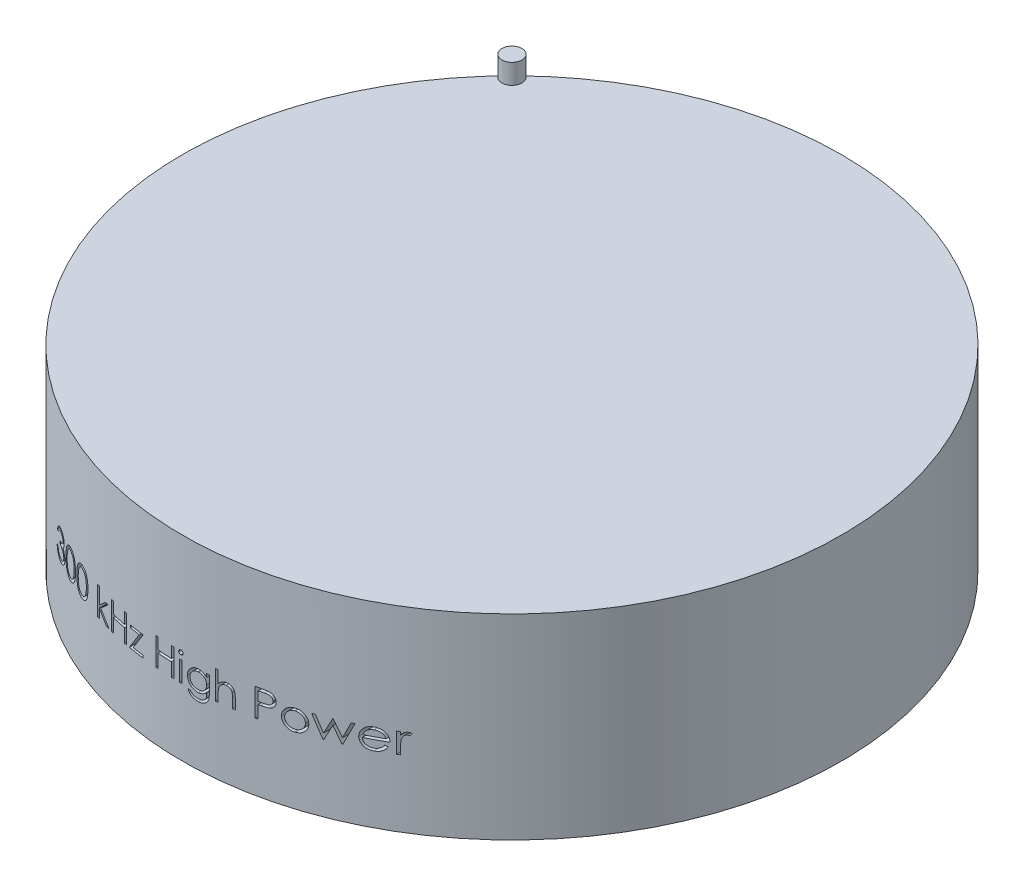
SolidWorks part; units mm, degrees
ref_plane "Front Plane" through (0, 0, 0) normal (0, 0, 1) x (1, 0, 0)
ref_plane "Top Plane" through (0, 0, 0) normal (0, 1, 0) x (1, 0, 0)
ref_plane "Right Plane" through (0, 0, 0) normal (1, 0, 0) x (0, 0, -1)
sketch "Sketch1" plane through (0, 0, 0) normal (0, 0, 1) x (1, 0, 0)
  line L0 (0, 0) -> (0, 29.7209) construction
  line L2 (0, 0) -> (41.9, 0)
  line L3 (0, 0) -> (0, 24.892)
  line L4 (0, 24.892) -> (41.9, 24.892)
  line L5 (41.9, 0) -> (41.9, 24.892)
  dimension "D1" = 83.8
  dimension "D2" = 24.892
revolve "Revolve1" add sketch "Sketch1" angle 360 about L0
sketch "Sketch2" plane through (0, 0, 0) normal (1, 0, 0) x (0, 0, -1)
  line L0 (0, 0) -> (0, 89.4138) construction
  line L2 (0, 56.896) -> (-1.27, 56.896)
  line L3 (0, 56.896) -> (0, 54.356)
  line L4 (0, 54.356) -> (-1.27, 54.356)
  line L5 (-1.27, 56.896) -> (-1.27, 54.356)
  line L6 (41.9, 24.892) -> (-41.9, 24.892) construction
  point P7 (0, 55.626)
  dimension "D1" = 1.27
  dimension "D2" = 2.54
  dimension "D3" = 30.734
revolve "Revolve2" add sketch "Sketch2" angle 360 about L0
sketch "Sketch3" plane through (0, 0, 0) normal (0, 0, 1) x (1, 0, 0)
  line L0 (-41.9, 8.5239) -> (41.9, 8.5239) construction
  line L1 (-41.9, 24.892) -> (-41.9, 0) construction
  line L2 (41.9, 0) -> (41.9, 24.892) construction
  text T0 "300 kHz High Power"
extrude "Cut-Extrude1" cut sketch "Sketch3" against normal blind 12.7 from offset 43.18
ref_plane "Plane1" through (0, 55.626, 0) normal (0, -1, 0) x (-1, 0, 0)
